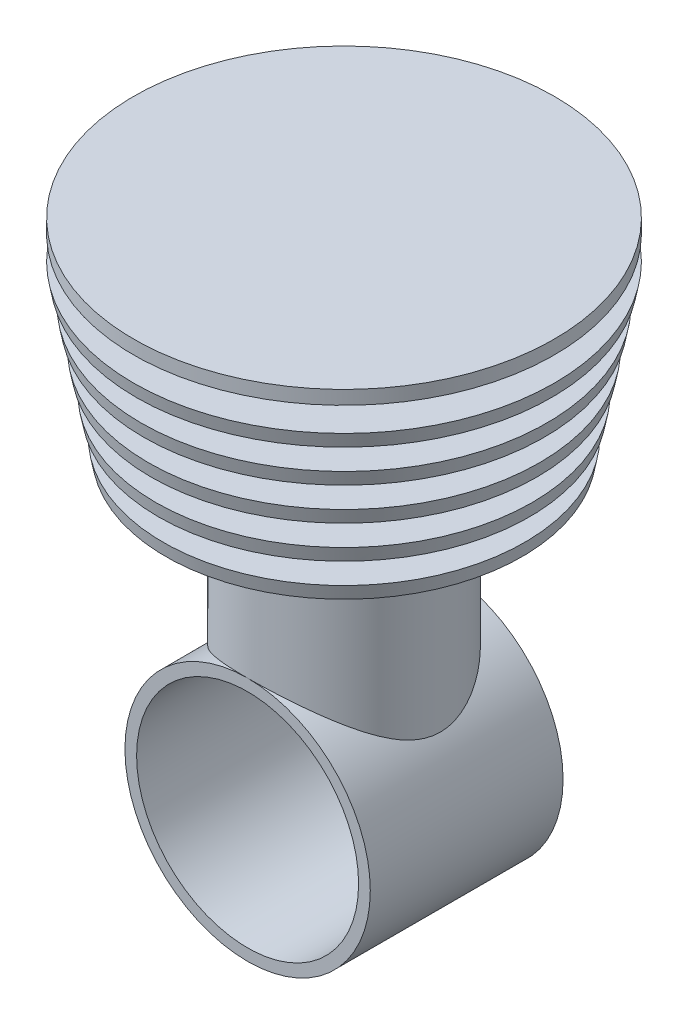
SolidWorks part; units mm, degrees
ref_plane "Plan de face" through (0, 0, 0) normal (0, 0, 1) x (1, 0, 0)
ref_plane "Plan de dessus" through (0, 0, 0) normal (0, 1, 0) x (1, 0, 0)
ref_plane "Plan de droite" through (0, 0, 0) normal (1, 0, 0) x (0, 0, -1)
sketch "Esquisse1" plane through (0, 0, 0) normal (1, 0, 0) x (0, 0, -1)
  line L0 (0, 0) -> (0, -21) construction
  line L1 (16.5, 0) -> (-16.5, 0)
  line L2 (16.5, 0) -> (16.5, -2)
  line L3 (16.5, -2) -> (-16.5, -2)
  line L4 (-16.5, -2) -> (-16.5, 0)
  line L5 (0, -21) -> (9.3299, -21) construction
  point P6 (0, 0)
  dimension "D1" = 21
  dimension "D2" = 33
  dimension "D3" = 2
revolve "Révolution1" add sketch "Esquisse1" angle 360 about L5
sketch "Esquisse2" plane through (0, 0, 0) normal (1, 0, 0) x (0, 0, -1)
  line L0 (0, 0) -> (0, 60) construction
  line L1 (0, 60) -> (0, 56)
  line L2 (0, 60) -> (-36, 60)
  line L3 (0, 56) -> (-13.5, 56)
  line L4 (-16.5, 0) -> (-13.5, 0)
  line L5 (16.5, 0) -> (-16.5, 0) construction
  line L6 (-13.5, 56) -> (-13.5, 0)
  line L7 (-16.5, 0) -> (-16.5, 25)
  line L8 (-16.5, 25) -> (-36, 25)
  line L9 (-36, 25) -> (-36, 27.3589)
  line L10 (-36, 27.3589) -> (-16.5, 27.3589)
  line L11 (-16.5, 27.3589) -> (-16.5, 31.5282)
  line L12 (-16.5, 31.5282) -> (-36, 31.5282)
  line L13 (-36, 31.5282) -> (-36, 33.8871)
  line L14 (-36, 33.8871) -> (-16.5, 33.8871)
  line L15 (-16.5, 33.8871) -> (-16.5, 38.0564)
  line L16 (-16.5, 38.0564) -> (-36, 38.0564)
  line L17 (-36, 38.0564) -> (-36, 40.4153)
  line L18 (-36, 40.4153) -> (-23.5, 40.4153)
  line L19 (-23.5, 40.4153) -> (-23.5, 44.5847)
  line L20 (-23.5, 44.5847) -> (-36, 44.5847)
  line L21 (-36, 44.5847) -> (-36, 46.9436)
  line L22 (-36, 46.9436) -> (-23.5, 46.9436)
  line L23 (-23.5, 46.9436) -> (-23.5, 51.1129)
  line L24 (-23.5, 51.1129) -> (-36, 51.1129)
  line L25 (-36, 51.1129) -> (-36, 53.4718)
  line L26 (-36, 53.4718) -> (-23.5, 53.4718)
  line L27 (-23.5, 53.4718) -> (-23.5, 57.6411)
  line L28 (-23.5, 57.6411) -> (-36, 57.6411)
  line L29 (-36, 57.6411) -> (-36, 60)
  dimension "D1" = 60
  dimension "D2" = 4
  dimension "D3" = 36
  dimension "D4" = 13.5
  dimension "D5" = 3
  dimension "D6" = 25
  dimension "D7" = 19.5
  dimension "D8" = 12.5
  dimension "D9" = 2.3589
revolve "Révolution2" add sketch "Esquisse2" angle 360 about L0
sketch "Esquisse3" plane through (0, 0, 0) normal (1, 0, 0) x (0, 0, -1)
  line L0 (-16.5, 25) -> (-30.5, 25) construction
  line L1 (-36, 25) -> (36, 25) construction
  line L2 (-36, 60) -> (-36, 53.4718)
  line L3 (-36, 53.4718) -> (-30.5, 25)
  line L4 (-30.5, 25) -> (-41.8796, 25)
  line L5 (-41.8796, 25) -> (-41.8796, 60)
  line L6 (-41.8796, 60) -> (-36, 60)
  line L7 (0, 0) -> (0, 63.2844) construction
  dimension "D1" = 14
revolve "Enlèvement de matière-Révolution1" cut sketch "Esquisse3" angle 360 about L7
sketch "Esquisse4" plane through (0, 0, 0) normal (0, -1, 0) x (1, 0, 0)
  circle A0 centre (0, 0) radius 16.5 construction
  circle A1 centre (0, 0) radius 13.5 construction
  circle A2 centre (0, 0) radius 16.5
  circle A3 centre (0, 0) radius 13.5
extrude "Boss.-Extru.1" add sketch "Esquisse4" along normal up to body separate body
sketch "Esquisse7" plane through (0, 0, 0) normal (0, 1, 0) x (1, 0, 0)
  circle A1 centre (0, 0) radius 13.5
  circle A2 centre (0, 0) radius 13.5
  dimension "D1" = 0
extrude "Enlèv. mat.-Extru.1" cut sketch "Esquisse7" against normal up to next contours A2
